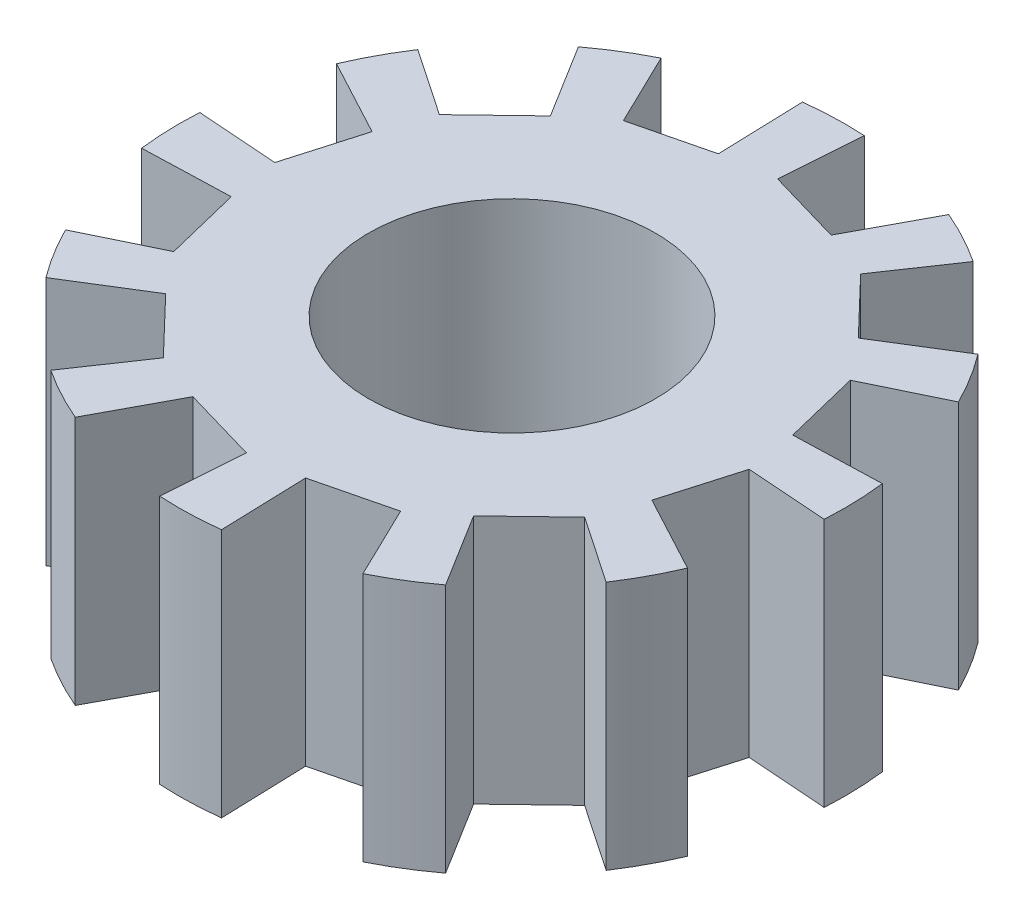
SolidWorks part; units mm, degrees
ref_plane "Plan de face" through (0, 0, 0) normal (0, 0, 1) x (1, 0, 0)
ref_plane "Plan de dessus" through (0, 0, 0) normal (0, 1, 0) x (1, 0, 0)
ref_plane "Plan de droite" through (0, 0, 0) normal (1, 0, 0) x (0, 0, -1)
sketch "Esquisse1" plane through (0, 0, 0) normal (0, 1, 0) x (1, 0, 0)
  circle A0 centre (0, 0) radius 2.3
  circle A1 centre (0, 0) radius 6
  dimension "D1" = 4.6
  dimension "D2" = 12
extrude "Boss.-Extru.1" add sketch "Esquisse1" along normal blind 4
sketch "Esquisse2" plane through (0, 4, 0) normal (0, 1, 0) x (1, 0, 0)
  line L0 (0.3704, 5.9886) -> (0.2273, 4.0292)
  line L1 (0.2273, 4.0292) -> (1.4359, 3.6783)
  line L2 (1.4359, 3.6783) -> (2.4087, 5.4953)
  line L3 (0.3704, 5.9886) -> (1.7927, 6.0718)
  line L4 (1.7927, 6.0718) -> (2.4087, 5.4953)
  line L5 (3.315, 5.001) -> (2.2115, 3.3757)
  line L6 (2.2115, 3.3757) -> (3.0827, 2.4675)
  line L7 (3.0827, 2.4675) -> (4.8336, 3.5547)
  line L8 (3.315, 5.001) -> (4.5884, 4.362)
  line L9 (4.5884, 4.362) -> (4.8336, 3.5547)
  line L10 (5.3714, 2.6735) -> (3.603, 1.8177)
  line L11 (3.603, 1.8177) -> (3.9034, 0.5956)
  line L12 (3.9034, 0.5956) -> (5.9634, 0.6617)
  line L13 (5.3714, 2.6735) -> (6.1547, 1.4834)
  line L14 (6.1547, 1.4834) -> (5.9634, 0.6617)
  line L15 (5.9886, -0.3704) -> (4.0292, -0.2273)
  line L16 (4.0292, -0.2273) -> (3.6783, -1.4359)
  line L17 (3.6783, -1.4359) -> (5.4953, -2.4087)
  line L18 (5.9886, -0.3704) -> (6.0718, -1.7927)
  line L19 (6.0718, -1.7927) -> (5.4953, -2.4087)
  line L20 (5.001, -3.315) -> (3.3757, -2.2115)
  line L21 (3.3757, -2.2115) -> (2.4675, -3.0827)
  line L22 (2.4675, -3.0827) -> (3.5547, -4.8336)
  line L23 (5.001, -3.315) -> (4.362, -4.5884)
  line L24 (4.362, -4.5884) -> (3.5547, -4.8336)
  line L25 (2.6735, -5.3714) -> (1.8177, -3.603)
  line L26 (1.8177, -3.603) -> (0.5956, -3.9034)
  line L27 (0.5956, -3.9034) -> (0.6617, -5.9634)
  line L28 (2.6735, -5.3714) -> (1.4834, -6.1547)
  line L29 (1.4834, -6.1547) -> (0.6617, -5.9634)
  line L30 (-0.3704, -5.9886) -> (-0.2273, -4.0292)
  line L31 (-0.2273, -4.0292) -> (-1.4359, -3.6783)
  line L32 (-1.4359, -3.6783) -> (-2.4087, -5.4953)
  line L33 (-0.3704, -5.9886) -> (-1.7927, -6.0718)
  line L34 (-1.7927, -6.0718) -> (-2.4087, -5.4953)
  line L35 (-3.315, -5.001) -> (-2.2115, -3.3757)
  line L36 (-2.2115, -3.3757) -> (-3.0827, -2.4675)
  line L37 (-3.0827, -2.4675) -> (-4.8336, -3.5547)
  line L38 (-3.315, -5.001) -> (-4.5884, -4.362)
  line L39 (-4.5884, -4.362) -> (-4.8336, -3.5547)
  line L40 (-5.3714, -2.6735) -> (-3.603, -1.8177)
  line L41 (-3.603, -1.8177) -> (-3.9034, -0.5956)
  line L42 (-3.9034, -0.5956) -> (-5.9634, -0.6617)
  line L43 (-5.3714, -2.6735) -> (-6.1547, -1.4834)
  line L44 (-6.1547, -1.4834) -> (-5.9634, -0.6617)
  line L45 (-5.9886, 0.3704) -> (-4.0292, 0.2273)
  line L46 (-4.0292, 0.2273) -> (-3.6783, 1.4359)
  line L47 (-3.6783, 1.4359) -> (-5.4953, 2.4087)
  line L48 (-5.9886, 0.3704) -> (-6.0718, 1.7927)
  line L49 (-6.0718, 1.7927) -> (-5.4953, 2.4087)
  line L50 (-5.001, 3.315) -> (-3.3757, 2.2115)
  line L51 (-3.3757, 2.2115) -> (-2.4675, 3.0827)
  line L52 (-2.4675, 3.0827) -> (-3.5547, 4.8336)
  line L53 (-5.001, 3.315) -> (-4.362, 4.5884)
  line L54 (-4.362, 4.5884) -> (-3.5547, 4.8336)
  line L55 (-2.6735, 5.3714) -> (-1.8177, 3.603)
  line L56 (-1.8177, 3.603) -> (-0.5956, 3.9034)
  line L57 (-0.5956, 3.9034) -> (-0.6617, 5.9634)
  line L58 (-2.6735, 5.3714) -> (-1.4834, 6.1547)
  line L59 (-1.4834, 6.1547) -> (-0.6617, 5.9634)
  circle A0 centre (0, 0) radius 6 construction
  dimension "D1" = 12
extrude "Enlèv. mat.-Extru.1" cut sketch "Esquisse2" against normal blind 4
sketch "Esquisse3" plane through (0, 4, 0) normal (0, 1, 0) x (1, 0, 0)
  circle A0 centre (0, 0) radius 5.3339
  circle A1 centre (0, 0) radius 6.9513
extrude "Enlèv. mat.-Extru.2" cut sketch "Esquisse3" against normal blind 10 and the other way blind 10
